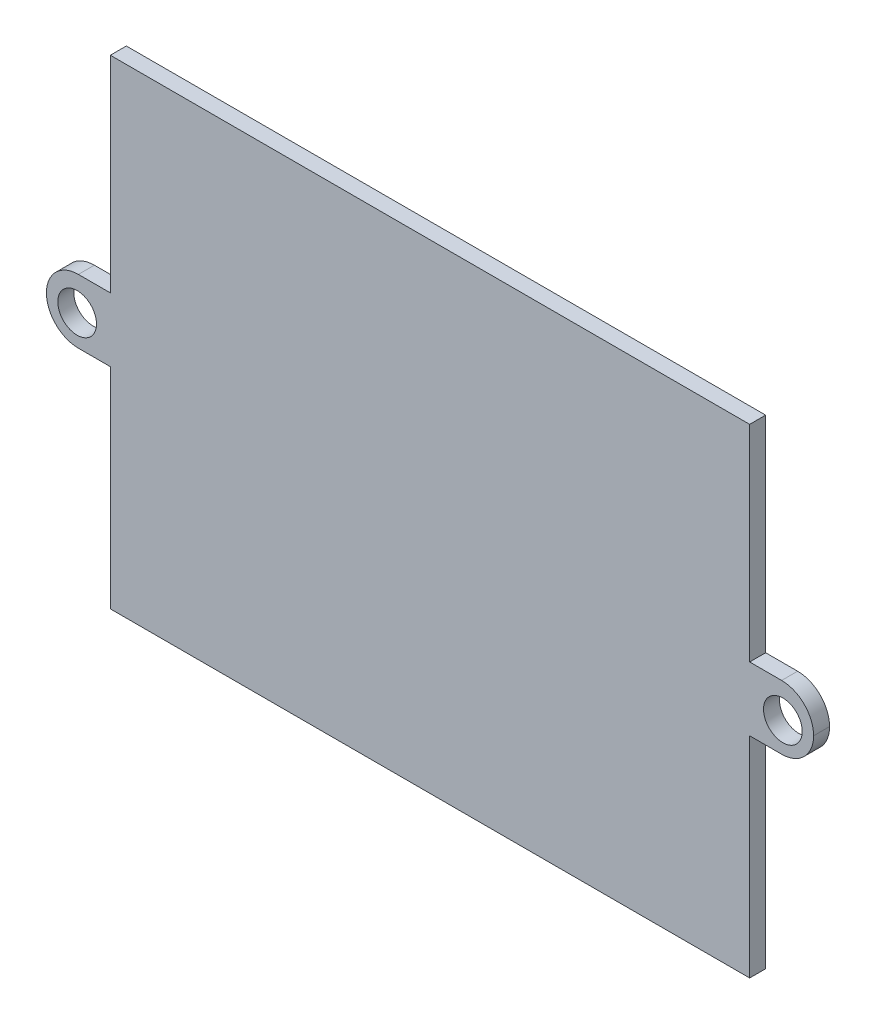
SolidWorks part; units mm, degrees
ref_plane "前视基准面" through (0, 0, 0) normal (0, 0, 1) x (1, 0, 0)
ref_plane "上视基准面" through (0, 0, 0) normal (0, 1, 0) x (1, 0, 0)
ref_plane "右视基准面" through (0, 0, 0) normal (1, 0, 0) x (0, 0, -1)
other "Configuration Table"
sketch "草图1" plane through (0, 0, 0) normal (0, 0, 1) x (1, 0, 0)
  line L1 (-100, 75) -> (100, 75)
  line L2 (-100, 75) -> (-100, -75)
  line L3 (-100, -75) -> (100, -75)
  line L4 (100, 75) -> (100, -75)
  line L5 (-100, 75) -> (100, -75) construction
  line L6 (-100, -75) -> (100, 75) construction
  point P0 (0, 0)
  dimension "D1" = 200
  dimension "D2" = 150
extrude "凸台-拉伸1" add sketch "草图1" along normal blind 5
sketch "草图2" plane through (0, 0, 0) normal (0, 0, 1) x (1, 0, 0)
  line L0 (-100, 75) -> (-100, -75) construction
  line L1 (-100, 10.6212) -> (-120, 10.6212)
  line L2 (-100, 10.6212) -> (-100, -9.3788)
  line L3 (-100, -9.3788) -> (-120, -9.3788)
  line L4 (-120, 10.6212) -> (-120, -9.3788)
  line L8 (120, 10.6212) -> (120, -9.3788)
  line L9 (100, -9.3788) -> (120, -9.3788)
  line L10 (100, 10.6212) -> (100, -9.3788)
  line L11 (100, 10.6212) -> (120, 10.6212)
  circle A0 centre (-110.3882, 0) radius 6.0544
  circle A1 centre (110.3882, 0) radius 6.0544
  dimension "D1" = 20
  dimension "D2" = 20
extrude "凸台-拉伸2" add sketch "草图2" along normal blind 5
fillet "圆角1" radius 10 4 edges at (120, -9.3788, 2.5) (120, 10.6212, 2.5) (-120, -9.3788, 2.5) (-120, 10.6212, 2.5)
